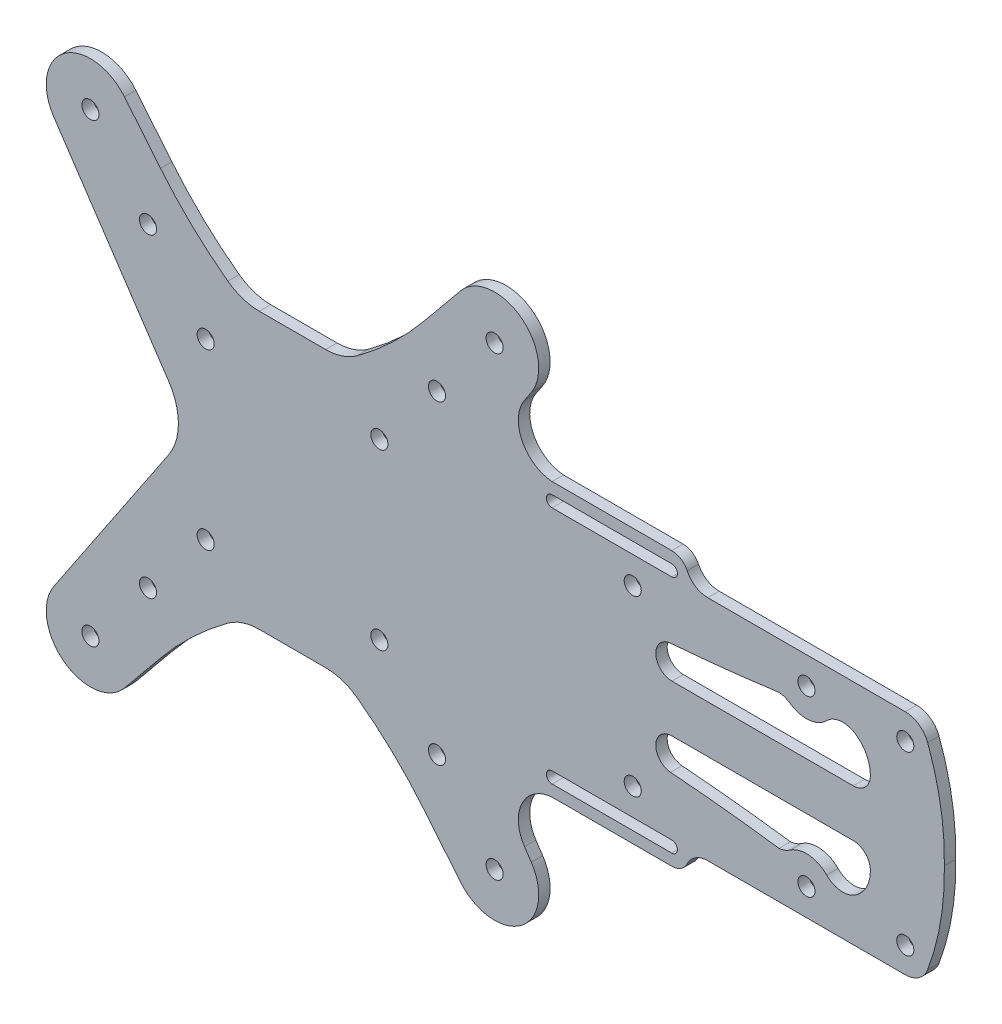
SolidWorks part; units mm, degrees
ref_plane "Alzado" through (0, 0, 0) normal (0, 0, 1) x (1, 0, 0)
ref_plane "Planta" through (0, 0, 0) normal (0, 1, 0) x (1, 0, 0)
ref_plane "Vista lateral" through (0, 0, 0) normal (1, 0, 0) x (0, 0, -1)
sketch "Croquis1" plane through (0, 0, 0) normal (0, 0, 1) x (1, 0, 0)
  line L0 (-41.9317, 35.7196) -> (-21.7292, 5.5661)
  line L1 (29.5025, -44.95) -> (23.1779, -37.2438)
  line L2 (-21.7292, -5.5661) -> (-41.9317, -35.7196)
  line L3 (0, -24.1955) -> (5.8264, -24.1955)
  line L4 (107.6126, 20) -> (72.9212, 20)
  line L5 (41.9317, -35.7196) -> (40.7426, -33.9448)
  line L6 (98.4739, 4.166) -> (66.6296, 4.166)
  line L7 (-29.5025, -44.95) -> (-23.1777, -37.2438)
  line L8 (40.7426, 33.9448) -> (41.9317, 35.7196)
  line L9 (45.5967, -24) -> (66.5967, -24)
  line L10 (29.5025, 44.95) -> (23.1777, 37.2438)
  line L11 (66.5967, -22) -> (45.5967, -22)
  line L12 (-23.1779, 37.2438) -> (-29.5025, 44.95)
  line L13 (0, 24.1955) -> (-5.8264, 24.1955)
  line L15 (66.5967, 24) -> (45.5967, 24)
  line L16 (-5.8264, -24.1955) -> (0, -24.1955)
  line L17 (45.5967, -20) -> (66.5967, -20)
  line L18 (5.8264, 24.1955) -> (0, 24.1955)
  line L19 (66.5967, 22) -> (45.5967, 22)
  line L21 (98.4739, -4.166) -> (66.6296, -4.166)
  line L22 (45.5967, 20) -> (66.5967, 20)
  line L23 (72.9212, -20) -> (107.6126, -20)
  circle A0 centre (59.75, -15.25) radius 1.5
  circle A1 centre (-15.25, -15.25) radius 1.5
  arc A2 (41.9317, 35.7196) -> (29.5025, 44.95) centre (35.4932, 40.0333) ccw
  arc A3 (5.8264, 24.1955) -> (11.353, 26.0087) centre (5.8264, 33.5248) ccw
  arc A4 (45.5967, -24) -> (40.7426, -33.9448) centre (46.0592, -30.3827) ccw
  circle A5 centre (35.4932, -40.0333) radius 1.5
  arc A6 (40.7426, 33.9448) -> (45.5967, 24) centre (46.0592, 30.3827) ccw
  arc A7 (-23.1779, 37.2438) -> (-11.353, 26.0087) centre (27.1524, 78.376) ccw
  arc A8 (98.9953, 12.1622) -> (93.8054, 11.7345) centre (96.6498, 8.922) ccw
  arc A9 (87.384, 11.1529) -> (93.8054, 11.7345) centre (90.25, 15.25) ccw
  circle A10 centre (107.6126, -15.5) radius 1.5
  arc A11 (101.4708, -7.03) -> (98.4739, -4.166) centre (98.4739, -7.166) ccw
  arc A12 (66.409, 9.8185) -> (66.6296, 4.166) centre (66.6296, 6.9965) ccw
  circle A13 centre (-35.4932, -40.0333) radius 1.5
  arc A14 (111.5451, 17.2675) -> (107.6126, 20) centre (107.6126, 15.804) ccw
  arc A15 (-21.7292, -5.5661) -> (-21.7292, 5.5661) centre (-30.037, 0) ccw
  arc A16 (93.8054, -11.7345) -> (98.9953, -12.1622) centre (96.6498, -8.922) ccw
  arc A17 (114.474, 0) -> (111.5451, 17.2675) centre (67.8434, 0.9728) ccw
  arc A18 (98.4739, 4.166) -> (101.4708, 7.03) centre (98.4739, 7.166) ccw
  arc A19 (98.9953, -12.1622) -> (101.4708, -7.03) centre (95.477, -7.302) ccw
  arc A20 (45.5967, -20) -> (45.5967, -22) centre (45.5967, -21) ccw
  circle A21 centre (15.25, 15.25) radius 1.5
  arc A22 (69.3072, 22.2857) -> (66.5967, 24) centre (66.5967, 21) ccw
  arc A23 (87.384, 11.1529) -> (85.4465, 11.8595) centre (85.0912, 7.8753) ccw
  arc A24 (85.4465, -11.8595) -> (66.409, -9.8185) centre (40.5006, -341.2912) ccw
  arc A25 (69.3072, 22.2857) -> (72.9212, 20) centre (72.9212, 24) ccw
  arc A26 (-11.353, -26.0087) -> (-23.1777, -37.2438) centre (27.1528, -78.3757) ccw
  arc A27 (111.5451, -17.2675) -> (114.474, 0) centre (67.8434, -0.9728) ccw
  circle A28 centre (59.75, 15.25) radius 1.5
  circle A29 centre (-25.3716, -27.6416) radius 1.5
  circle A30 centre (-25.3716, 27.6416) radius 1.5
  arc A31 (-29.5025, 44.95) -> (-41.9317, 35.7196) centre (-35.4932, 40.0333) ccw
  circle A32 centre (35.4932, 40.0333) radius 1.5
  arc A33 (-11.353, 26.0087) -> (-5.8264, 24.1955) centre (-5.8264, 33.5248) ccw
  circle A34 centre (107.6126, 15.5) radius 1.5
  circle A35 centre (-35.4932, 40.0333) radius 1.5
  arc A36 (66.5967, 20) -> (66.5967, 22) centre (66.5967, 21) ccw
  circle A37 centre (90.25, -15.25) radius 1.5
  arc A38 (-5.8264, -24.1955) -> (-11.353, -26.0087) centre (-5.8264, -33.5248) ccw
  arc A39 (72.9212, -20) -> (69.3072, -22.2857) centre (72.9212, -24) ccw
  arc A40 (66.5967, -24) -> (69.3072, -22.2857) centre (66.5967, -21) ccw
  arc A41 (29.5025, -44.95) -> (41.9317, -35.7196) centre (35.4932, -40.0333) ccw
  arc A42 (85.4465, -11.8595) -> (87.384, -11.1529) centre (85.0912, -7.8753) ccw
  arc A43 (66.6296, -4.166) -> (66.409, -9.8185) centre (66.6296, -6.9965) ccw
  arc A44 (93.8054, -11.7345) -> (87.384, -11.1529) centre (90.25, -15.25) ccw
  arc A45 (11.353, -26.0087) -> (5.8264, -24.1955) centre (5.8264, -33.5248) ccw
  arc A46 (66.409, 9.8185) -> (85.4465, 11.8595) centre (40.5006, 341.2912) ccw
  circle A47 centre (90.25, 15.25) radius 1.5
  circle A48 centre (-15.25, 15.25) radius 1.5
  arc A49 (23.1779, -37.2438) -> (11.353, -26.0087) centre (-27.1524, -78.376) ccw
  circle A51 centre (25.3716, -27.6416) radius 1.5
  arc A52 (-41.9317, -35.7196) -> (-29.5025, -44.95) centre (-35.4932, -40.0333) ccw
  circle A53 centre (15.25, -15.25) radius 1.5
  circle A54 centre (25.3716, 27.6416) radius 1.5
  arc A55 (11.353, 26.0087) -> (23.1777, 37.2438) centre (-27.1528, 78.3757) ccw
  arc A56 (101.4708, 7.03) -> (98.9953, 12.1622) centre (95.477, 7.302) ccw
  arc A57 (45.5967, 22) -> (45.5967, 20) centre (45.5967, 21) ccw
  arc A58 (107.6126, -20) -> (111.5451, -17.2675) centre (107.6126, -15.804) ccw
  arc A59 (66.5967, -22) -> (66.5967, -20) centre (66.5967, -21) ccw
  point P3 (0, 0)
  point P4 (0, 0)
  point P5 (0, 0)
  point P6 (0, 0)
  point P7 (0, 0)
  point P8 (0, 0)
  point P9 (0, 0)
  point P10 (0, 0)
  point P11 (0, 0)
  point P12 (0, 0)
  point P13 (0, 0)
  point P14 (0, 0)
  point P15 (0, 0)
  point P16 (0, 0)
  point P17 (0, 0)
  point P18 (0, 0)
  point P19 (0, 0)
  point P20 (0, 0)
  point P21 (0, 0)
  point P22 (0, 0)
  point P23 (0, 0)
  point P24 (0, 0)
  point P25 (0, 0)
  point P26 (0, 0)
  point P27 (0, 0)
  point P28 (0, 0)
  point P29 (0, 0)
  point P30 (0, 0)
  point P31 (0, 0)
  point P32 (0, 0)
  point P33 (0, 0)
  point P34 (0, 0)
  point P35 (0, 0)
  point P36 (0, 0)
  point P37 (0, 0)
  point P38 (0, 0)
  point P39 (0, 0)
  point P40 (0, 0)
  point P41 (0, 0)
  point P42 (0, 0)
  point P43 (0, 0)
  point P44 (0, 0)
  point P45 (0, 0)
  point P46 (0, 0)
  point P47 (0, 0)
  point P48 (0, 0)
  point P49 (0, 0)
  point P50 (0, 0)
  point P51 (0, 0)
  point P52 (0, 0)
  point P53 (0, 0)
  point P54 (0, 0)
  point P55 (0, 0)
  point P56 (0, 0)
  point P57 (0, 0)
  point P58 (0, 0)
  point P59 (0, 0)
  point P60 (0, 0)
  point P61 (0, 0)
  point P62 (0, 0)
  point P63 (0, 0)
  point P64 (0, 0)
  point P65 (0, 0)
  point P66 (0, 0)
  point P67 (0, 0)
  point P68 (0, 0)
  point P69 (0, 0)
  point P70 (0, 0)
  point P71 (0, 0)
  point P72 (0, 0)
  point P73 (0, 0)
  point P74 (0, 0)
  point P75 (0, 0)
  point P76 (0, 0)
  point P77 (0, 0)
  point P78 (0, 0)
  point P79 (0, 0)
  point P80 (0, 0)
  point P81 (0, 0)
  point P82 (0, 0)
  point P83 (0, 0)
  point P84 (0, 0)
  point P85 (0, 0)
  point P86 (0, 0)
  point P87 (0, 0)
  point P88 (0, 0)
  point P89 (0, 0)
  point P90 (0, 0)
  point P91 (0, 0)
  point P92 (0, 0)
  point P93 (0, 0)
  point P94 (0, 0)
  point P95 (0, 0)
  point P96 (0, 0)
  point P97 (0, 0)
  point P98 (0, 0)
  point P99 (0, 0)
  point P100 (0, 0)
  point P101 (0, 0)
  point P102 (0, 0)
  point P103 (0, 0)
  point P104 (0, 0)
  point P105 (0, 0)
  point P106 (0, 0)
  point P107 (0, 0)
  point P108 (0, 0)
  point P109 (0, 0)
  point P110 (0, 0)
  point P111 (0, 0)
  point P112 (0, 0)
  point P113 (0, 0)
  point P114 (0, 0)
  point P115 (0, 0)
  point P116 (0, 0)
  point P117 (0, 0)
  point P118 (0, 0)
  point P119 (0, 0)
  point P120 (0, 0)
  point P121 (0, 0)
  point P122 (0, 0)
  point P123 (0, 0)
  point P124 (0, 0)
  point P125 (0, 0)
  point P126 (0, 0)
  point P127 (0, 0)
  point P128 (0, 0)
  point P129 (0, 0)
  point P130 (0, 0)
  point P131 (0, 0)
  point P132 (0, 0)
  point P133 (0, 0)
  point P134 (0, 0)
  point P135 (0, 0)
  point P136 (0, 0)
  point P137 (0, 0)
  point P138 (0, 0)
  point P139 (0, 0)
  point P140 (0, 0)
  point P141 (0, 0)
  point P142 (0, 0)
  point P143 (0, 0)
  point P144 (0, 0)
  point P145 (0, 0)
  point P146 (0, 0)
  point P147 (0, 0)
  point P148 (0, 0)
  point P149 (0, 0)
  point P150 (0, 0)
  point P151 (0, 0)
  point P152 (0, 0)
  point P153 (0, 0)
  point P154 (0, 0)
  point P155 (0, 0)
  point P156 (0, 0)
  point P157 (0, 0)
  point P158 (0, 0)
  point P159 (0, 0)
  point P160 (0, 0)
  point P161 (0, 0)
  point P162 (0, 0)
  point P163 (0, 0)
  point P164 (0, 0)
  point P165 (0, 0)
  point P166 (0, 0)
  point P167 (0, 0)
  point P168 (0, 0)
  point P169 (0, 0)
  point P170 (0, 0)
  point P171 (0, 0)
  point P172 (0, 0)
  point P173 (0, 0)
  point P174 (0, 0)
  point P175 (0, 0)
  point P176 (0, 0)
  point P177 (0, 0)
  point P178 (0, 0)
  point P179 (0, 0)
  point P180 (0, 0)
  point P181 (0, 0)
  point P182 (0, 0)
  point P183 (0, 0)
  point P184 (0, 0)
  point P185 (0, 0)
  point P186 (0, 0)
  point P187 (0, 0)
  point P188 (0, 0)
  point P189 (0, 0)
  point P190 (0, 0)
  point P191 (0, 0)
  point P192 (0, 0)
  point P193 (0, 0)
  point P194 (0, 0)
  point P195 (0, 0)
  point P196 (0, 0)
  point P197 (0, 0)
  point P198 (0, 0)
  point P199 (0, 0)
  point P200 (0, 0)
  point P201 (0, 0)
  point P202 (0, 0)
  point P203 (0, 0)
  point P204 (0, 0)
  point P205 (0, 0)
  point P206 (0, 0)
  point P207 (0, 0)
  point P208 (0, 0)
  point P209 (0, 0)
  point P210 (0, 0)
  point P211 (0, 0)
  point P212 (0, 0)
  point P213 (0, 0)
  point P214 (0, 0)
  point P215 (0, 0)
  point P216 (0, 0)
  point P217 (0, 0)
  point P218 (0, 0)
  point P219 (0, 0)
  point P220 (0, 0)
  point P221 (0, 0)
  point P222 (0, 0)
  point P223 (0, 0)
  point P224 (0, 0)
  point P225 (0, 0)
  point P226 (0, 0)
  point P227 (0, 0)
  point P228 (0, 0)
  point P229 (0, 0)
  point P230 (0, 0)
  point P231 (0, 0)
  point P232 (0, 0)
  point P233 (0, 0)
  point P234 (0, 0)
  point P235 (0, 0)
  point P236 (0, 0)
  point P237 (0, 0)
  point P238 (0, 0)
  point P239 (0, 0)
  point P240 (0, 0)
  point P241 (0, 0)
  point P242 (0, 0)
  point P243 (0, 0)
  point P244 (0, 0)
  point P245 (0, 0)
  point P246 (0, 0)
  point P247 (0, 0)
  point P248 (0, 0)
  point P249 (0, 0)
  point P250 (0, 0)
  point P251 (0, 0)
  point P252 (0, 0)
  point P253 (0, 0)
  point P254 (0, 0)
  point P255 (0, 0)
  point P256 (0, 0)
  point P257 (0, 0)
  point P258 (0, 0)
  point P259 (0, 0)
  point P260 (0, 0)
  point P261 (0, 0)
  point P262 (0, 0)
  point P263 (0, 0)
  point P264 (0, 0)
  point P265 (0, 0)
  point P266 (0, 0)
  point P267 (0, 0)
  point P268 (0, 0)
  point P269 (0, 0)
  point P270 (0, 0)
  point P271 (0, 0)
  point P272 (0, 0)
  point P273 (0, 0)
  point P274 (0, 0)
  point P275 (0, 0)
  point P276 (0, 0)
  point P277 (0, 0)
  point P278 (0, 0)
  point P279 (0, 0)
  point P280 (0, 0)
  point P281 (0, 0)
  point P282 (0, 0)
  point P283 (0, 0)
  point P284 (0, 0)
  point P285 (0, 0)
  point P286 (0, 0)
  point P287 (0, 0)
  point P288 (0, 0)
  point P289 (0, 0)
  point P290 (0, 0)
  point P291 (0, 0)
  point P292 (0, 0)
  point P293 (0, 0)
  point P294 (0, 0)
  point P295 (0, 0)
  point P296 (0, 0)
  point P297 (0, 0)
  point P298 (0, 0)
  point P299 (0, 0)
  point P300 (0, 0)
  point P301 (0, 0)
  point P302 (0, 0)
  point P303 (0, 0)
  point P304 (0, 0)
  point P305 (0, 0)
  point P306 (0, 0)
  point P307 (0, 0)
  point P308 (0, 0)
  point P309 (0, 0)
  point P310 (0, 0)
  point P311 (0, 0)
  point P312 (0, 0)
  point P313 (0, 0)
  point P314 (0, 0)
  point P315 (0, 0)
  point P316 (0, 0)
  point P317 (0, 0)
  point P318 (0, 0)
  point P319 (0, 0)
  point P320 (0, 0)
  point P321 (0, 0)
  point P322 (0, 0)
  point P323 (0, 0)
  point P324 (0, 0)
  point P325 (0, 0)
  point P326 (0, 0)
  point P327 (0, 0)
  point P328 (0, 0)
  point P329 (0, 0)
  point P330 (0, 0)
  point P331 (0, 0)
  point P332 (0, 0)
  point P333 (0, 0)
  point P334 (0, 0)
  point P335 (0, 0)
  point P336 (0, 0)
  point P337 (0, 0)
  point P338 (0, 0)
  point P339 (0, 0)
  point P340 (0, 0)
  point P341 (0, 0)
  point P342 (0, 0)
  point P343 (0, 0)
  point P344 (0, 0)
  point P345 (0, 0)
  point P346 (0, 0)
  point P347 (0, 0)
  point P348 (0, 0)
  point P349 (0, 0)
  point P350 (0, 0)
  point P351 (0, 0)
  point P352 (0, 0)
  point P353 (0, 0)
  point P354 (0, 0)
  point P355 (0, 0)
  point P356 (0, 0)
  point P357 (0, 0)
  point P358 (0, 0)
  point P359 (0, 0)
  point P360 (0, 0)
  point P361 (0, 0)
  point P362 (0, 0)
  point P363 (0, 0)
  point P364 (0, 0)
  point P365 (0, 0)
  point P366 (0, 0)
  point P367 (0, 0)
  point P368 (0, 0)
  point P369 (0, 0)
  point P370 (0, 0)
  point P371 (0, 0)
  point P372 (0, 0)
  point P373 (0, 0)
  point P374 (0, 0)
  point P375 (0, 0)
  point P376 (0, 0)
  point P377 (0, 0)
  point P378 (0, 0)
  point P379 (0, 0)
  point P380 (0, 0)
  point P381 (0, 0)
  point P382 (0, 0)
  point P383 (0, 0)
  point P384 (0, 0)
  point P385 (0, 0)
  point P386 (0, 0)
  point P387 (0, 0)
  point P388 (0, 0)
  point P389 (0, 0)
  point P390 (0, 0)
  point P391 (0, 0)
  point P392 (0, 0)
  point P393 (0, 0)
  point P394 (0, 0)
  point P395 (0, 0)
  point P396 (0, 0)
  point P397 (0, 0)
  point P398 (0, 0)
  point P399 (0, 0)
  point P400 (0, 0)
  point P401 (0, 0)
  point P402 (0, 0)
  point P403 (0, 0)
  point P404 (0, 0)
  point P405 (0, 0)
  point P406 (0, 0)
  point P407 (0, 0)
  point P408 (0, 0)
  point P409 (0, 0)
  point P410 (0, 0)
  point P411 (0, 0)
  point P412 (0, 0)
  point P413 (0, 0)
  point P414 (0, 0)
  point P415 (0, 0)
  point P416 (0, 0)
  point P417 (0, 0)
  point P418 (0, 0)
  point P419 (0, 0)
  point P420 (0, 0)
  point P421 (0, 0)
  point P422 (0, 0)
  point P423 (0, 0)
  point P424 (0, 0)
  point P425 (0, 0)
  point P426 (0, 0)
  point P427 (0, 0)
  point P428 (0, 0)
  point P429 (0, 0)
  point P430 (0, 0)
  point P431 (0, 0)
  point P432 (0, 0)
  point P433 (0, 0)
  point P434 (0, 0)
  point P435 (0, 0)
  point P436 (0, 0)
  point P437 (0, 0)
  point P438 (0, 0)
  point P439 (0, 0)
  point P440 (0, 0)
  point P441 (0, 0)
  point P442 (0, 0)
  point P443 (0, 0)
  point P444 (0, 0)
  point P445 (0, 0)
  point P446 (0, 0)
  point P447 (0, 0)
  point P448 (0, 0)
  point P449 (0, 0)
  point P450 (0, 0)
  point P451 (0, 0)
  point P452 (0, 0)
  point P453 (0, 0)
  point P454 (0, 0)
  point P455 (0, 0)
  point P456 (0, 0)
  point P457 (0, 0)
  point P458 (0, 0)
  point P459 (0, 0)
  point P460 (0, 0)
  point P461 (0, 0)
  point P462 (0, 0)
  point P463 (0, 0)
  point P464 (0, 0)
  point P465 (0, 0)
  point P466 (0, 0)
  point P467 (0, 0)
  point P468 (0, 0)
  point P469 (0, 0)
  point P470 (0, 0)
  point P471 (0, 0)
  point P472 (0, 0)
  point P473 (0, 0)
  point P474 (0, 0)
  point P475 (0, 0)
  point P476 (0, 0)
  point P477 (0, 0)
  point P478 (0, 0)
  point P479 (0, 0)
  point P480 (0, 0)
  point P481 (0, 0)
  point P482 (0, 0)
  point P483 (0, 0)
  point P484 (0, 0)
  point P485 (0, 0)
  point P486 (0, 0)
  point P487 (0, 0)
  point P488 (0, 0)
  point P489 (0, 0)
  point P490 (0, 0)
  point P491 (0, 0)
  point P492 (0, 0)
  point P493 (0, 0)
  point P494 (0, 0)
  point P495 (0, 0)
  point P496 (0, 0)
  point P497 (0, 0)
  point P498 (0, 0)
  point P499 (0, 0)
  point P500 (0, 0)
  point P501 (0, 0)
  point P502 (0, 0)
  point P503 (0, 0)
  point P504 (0, 0)
  point P505 (0, 0)
  point P506 (0, 0)
  point P507 (0, 0)
  point P508 (0, 0)
  point P509 (0, 0)
  point P510 (0, 0)
  point P511 (0, 0)
  point P512 (0, 0)
  point P513 (0, 0)
  point P514 (0, 0)
  point P515 (0, 0)
  point P516 (0, 0)
  point P517 (0, 0)
  point P518 (0, 0)
  point P519 (0, 0)
  point P520 (0, 0)
  point P521 (0, 0)
  point P522 (0, 0)
  point P523 (0, 0)
  point P524 (0, 0)
  point P525 (0, 0)
  point P526 (0, 0)
  point P527 (0, 0)
  point P528 (0, 0)
  point P529 (0, 0)
  point P530 (0, 0)
  point P531 (0, 0)
  point P532 (0, 0)
  point P533 (0, 0)
  point P534 (0, 0)
  point P535 (0, 0)
  point P536 (0, 0)
  point P537 (0, 0)
  point P538 (0, 0)
  point P539 (0, 0)
  point P540 (0, 0)
  point P541 (0, 0)
  point P542 (0, 0)
  point P543 (0, 0)
  point P544 (0, 0)
  point P545 (0, 0)
  point P546 (0, 0)
  point P547 (0, 0)
  point P548 (0, 0)
  point P549 (0, 0)
  point P550 (0, 0)
  point P551 (0, 0)
  point P552 (0, 0)
  point P553 (0, 0)
  point P554 (0, 0)
  point P555 (0, 0)
  point P556 (0, 0)
  point P557 (0, 0)
  point P558 (0, 0)
  point P559 (0, 0)
  point P560 (0, 0)
  point P561 (0, 0)
  point P562 (0, 0)
  point P563 (0, 0)
  point P564 (0, 0)
  point P565 (0, 0)
  point P566 (0, 0)
  point P567 (0, 0)
  point P568 (0, 0)
  point P569 (0, 0)
  point P570 (0, 0)
  point P571 (0, 0)
  point P572 (0, 0)
  point P573 (0, 0)
  point P574 (0, 0)
  point P575 (0, 0)
  point P576 (0, 0)
  point P577 (0, 0)
  point P578 (0, 0)
  point P579 (0, 0)
  point P580 (0, 0)
  point P581 (0, 0)
  point P582 (0, 0)
  point P583 (0, 0)
  point P584 (0, 0)
  point P585 (0, 0)
  point P586 (0, 0)
  point P587 (0, 0)
  point P588 (0, 0)
  point P589 (0, 0)
  point P590 (0, 0)
  point P591 (0, 0)
  point P592 (0, 0)
  point P593 (0, 0)
  point P594 (0, 0)
  point P595 (0, 0)
  point P596 (0, 0)
  point P597 (0, 0)
  point P598 (0, 0)
  point P599 (0, 0)
  point P600 (0, 0)
  point P601 (0, 0)
  point P602 (0, 0)
  point P603 (0, 0)
  point P604 (0, 0)
  point P605 (0, 0)
  point P606 (0, 0)
  point P607 (0, 0)
  point P608 (0, 0)
  point P609 (0, 0)
  point P610 (0, 0)
  point P611 (0, 0)
  point P612 (0, 0)
  point P613 (0, 0)
  point P614 (0, 0)
  point P615 (0, 0)
  point P616 (0, 0)
  point P617 (0, 0)
  point P618 (0, 0)
  point P619 (0, 0)
  point P620 (0, 0)
  point P621 (0, 0)
  point P622 (0, 0)
  point P623 (0, 0)
  point P624 (0, 0)
  point P625 (0, 0)
  point P626 (0, 0)
  point P627 (0, 0)
  point P628 (0, 0)
  point P629 (0, 0)
  point P630 (0, 0)
  point P631 (0, 0)
  point P632 (0, 0)
  point P633 (0, 0)
  point P634 (0, 0)
  point P635 (0, 0)
  point P636 (0, 0)
  point P637 (0, 0)
  point P638 (0, 0)
  point P639 (0, 0)
  point P640 (0, 0)
  point P641 (0, 0)
  point P642 (0, 0)
  point P643 (0, 0)
  point P644 (0, 0)
  point P645 (0, 0)
  point P646 (0, 0)
  point P647 (0, 0)
  point P648 (0, 0)
  point P649 (0, 0)
  point P650 (0, 0)
  point P651 (0, 0)
  point P652 (0, 0)
  point P653 (0, 0)
  point P654 (0, 0)
  point P655 (0, 0)
  point P656 (0, 0)
  point P657 (0, 0)
  point P658 (0, 0)
  point P659 (0, 0)
  point P660 (0, 0)
  point P661 (0, 0)
  point P662 (0, 0)
  point P663 (0, 0)
  point P664 (0, 0)
  point P665 (0, 0)
  point P666 (0, 0)
  point P667 (0, 0)
  point P668 (0, 0)
  point P669 (0, 0)
  point P670 (0, 0)
  point P671 (0, 0)
  point P672 (0, 0)
  point P673 (0, 0)
  point P674 (0, 0)
  point P675 (0, 0)
  point P676 (0, 0)
  point P677 (0, 0)
  point P678 (0, 0)
  point P679 (0, 0)
  point P680 (0, 0)
  point P681 (0, 0)
  point P682 (0, 0)
  point P683 (0, 0)
  point P684 (0, 0)
  point P685 (0, 0)
  point P686 (0, 0)
  point P687 (0, 0)
  point P688 (0, 0)
  point P689 (0, 0)
  point P690 (0, 0)
  point P691 (0, 0)
  point P692 (0, 0)
  point P693 (0, 0)
  point P694 (0, 0)
  point P695 (0, 0)
  point P696 (0, 0)
  point P697 (0, 0)
  point P698 (0, 0)
  point P699 (0, 0)
  point P700 (0, 0)
  point P701 (0, 0)
  point P702 (0, 0)
  point P703 (0, 0)
  point P704 (0, 0)
  point P705 (0, 0)
  point P706 (0, 0)
  point P707 (0, 0)
  point P708 (0, 0)
  point P709 (0, 0)
  point P710 (0, 0)
  point P711 (0, 0)
  point P712 (0, 0)
  point P713 (0, 0)
  point P714 (0, 0)
  point P715 (0, 0)
  point P716 (0, 0)
  point P717 (0, 0)
  point P718 (0, 0)
  point P719 (0, 0)
  point P720 (0, 0)
  point P721 (0, 0)
  point P722 (0, 0)
  point P723 (0, 0)
  point P724 (0, 0)
  point P725 (0, 0)
  point P726 (0, 0)
  point P727 (0, 0)
  point P728 (0, 0)
  point P729 (0, 0)
  point P730 (0, 0)
  point P731 (0, 0)
  point P732 (0, 0)
  point P733 (0, 0)
  point P734 (0, 0)
  point P735 (0, 0)
  point P736 (0, 0)
  point P737 (0, 0)
  point P738 (0, 0)
  point P739 (0, 0)
  point P740 (0, 0)
  point P741 (0, 0)
  point P742 (0, 0)
  point P743 (0, 0)
  point P744 (0, 0)
  point P745 (0, 0)
  point P746 (0, 0)
  point P747 (0, 0)
  point P748 (0, 0)
  point P749 (0, 0)
  point P750 (0, 0)
  point P751 (0, 0)
  point P752 (0, 0)
  point P753 (0, 0)
  point P754 (0, 0)
  point P755 (0, 0)
  point P756 (0, 0)
  point P757 (0, 0)
  point P758 (0, 0)
  point P759 (0, 0)
  point P760 (0, 0)
  point P761 (0, 0)
  point P762 (0, 0)
  point P763 (0, 0)
  point P764 (0, 0)
  point P765 (0, 0)
  point P766 (0, 0)
  point P767 (0, 0)
  point P768 (0, 0)
  point P769 (0, 0)
  point P770 (0, 0)
  point P771 (0, 0)
  point P772 (0, 0)
  point P773 (0, 0)
  point P774 (0, 0)
  point P775 (0, 0)
  point P776 (0, 0)
  point P777 (0, 0)
  point P778 (0, 0)
  point P779 (0, 0)
  point P780 (0, 0)
  point P781 (0, 0)
  point P782 (0, 0)
  point P783 (0, 0)
  point P784 (0, 0)
  point P785 (0, 0)
  point P786 (0, 0)
  point P787 (0, 0)
  point P788 (0, 0)
  point P789 (0, 0)
  point P790 (0, 0)
  point P791 (0, 0)
  point P792 (0, 0)
  point P793 (0, 0)
  point P794 (0, 0)
  point P795 (0, 0)
  point P796 (0, 0)
  point P797 (0, 0)
  point P798 (0, 0)
  point P799 (0, 0)
  point P800 (0, 0)
  point P801 (0, 0)
  point P802 (0, 0)
  point P803 (0, 0)
  point P804 (0, 0)
  point P805 (0, 0)
  point P806 (0, 0)
  point P807 (0, 0)
  point P808 (0, 0)
  point P809 (0, 0)
  point P810 (0, 0)
  point P811 (0, 0)
  point P812 (0, 0)
  point P813 (0, 0)
  point P814 (0, 0)
  point P815 (0, 0)
  point P816 (0, 0)
  point P817 (0, 0)
  point P818 (0, 0)
  point P819 (0, 0)
  point P820 (0, 0)
  point P821 (0, 0)
  point P822 (0, 0)
  point P823 (0, 0)
  point P824 (0, 0)
  point P825 (0, 0)
  point P826 (0, 0)
  point P827 (0, 0)
  point P828 (0, 0)
  point P829 (0, 0)
  point P830 (0, 0)
  point P831 (0, 0)
  point P832 (0, 0)
  point P833 (0, 0)
  point P834 (0, 0)
  point P835 (0, 0)
  point P836 (0, 0)
  point P837 (0, 0)
  point P838 (0, 0)
  point P839 (0, 0)
  point P840 (0, 0)
  point P841 (0, 0)
  point P842 (0, 0)
  point P843 (0, 0)
  point P844 (0, 0)
  point P845 (0, 0)
  point P846 (0, 0)
  point P847 (0, 0)
  point P848 (0, 0)
  point P849 (0, 0)
  point P850 (0, 0)
  point P851 (0, 0)
  point P852 (0, 0)
  point P853 (0, 0)
  point P854 (0, 0)
  point P855 (0, 0)
  point P856 (0, 0)
  point P857 (0, 0)
  point P858 (0, 0)
  point P859 (0, 0)
  point P860 (0, 0)
  point P861 (0, 0)
  point P862 (0, 0)
  point P863 (0, 0)
  point P864 (0, 0)
  point P865 (0, 0)
  point P866 (0, 0)
  point P867 (0, 0)
  point P868 (0, 0)
  point P869 (0, 0)
  point P870 (0, 0)
  point P871 (0, 0)
  point P872 (0, 0)
  point P873 (0, 0)
  point P874 (0, 0)
  point P875 (0, 0)
  point P876 (0, 0)
  point P877 (0, 0)
  point P878 (0, 0)
  point P879 (0, 0)
  point P880 (0, 0)
  point P881 (0, 0)
  point P882 (0, 0)
  point P883 (0, 0)
  point P884 (0, 0)
  point P885 (0, 0)
  point P886 (0, 0)
  point P887 (0, 0)
  point P888 (0, 0)
  point P889 (0, 0)
  point P890 (0, 0)
  point P891 (0, 0)
  point P892 (0, 0)
  point P893 (0, 0)
  point P894 (0, 0)
  point P895 (0, 0)
  point P896 (0, 0)
  point P897 (0, 0)
  point P898 (0, 0)
  point P899 (0, 0)
  point P900 (0, 0)
  point P901 (0, 0)
  point P902 (0, 0)
  point P903 (0, 0)
  point P904 (0, 0)
  point P905 (0, 0)
  point P906 (0, 0)
  point P907 (0, 0)
  point P908 (0, 0)
  point P909 (0, 0)
  point P910 (0, 0)
  point P911 (0, 0)
  point P912 (0, 0)
  point P913 (0, 0)
  point P914 (0, 0)
  point P915 (0, 0)
  point P916 (0, 0)
  point P917 (0, 0)
  point P918 (0, 0)
  point P919 (0, 0)
  point P920 (0, 0)
  point P921 (0, 0)
  point P922 (0, 0)
  point P923 (0, 0)
  point P924 (0, 0)
  point P925 (0, 0)
  point P926 (0, 0)
  point P927 (0, 0)
  point P928 (0, 0)
  point P929 (0, 0)
  point P930 (0, 0)
  point P931 (0, 0)
  point P932 (0, 0)
  point P933 (0, 0)
  point P934 (0, 0)
  point P935 (0, 0)
  point P936 (0, 0)
  point P937 (0, 0)
  point P938 (0, 0)
  point P939 (0, 0)
  point P940 (0, 0)
  point P941 (0, 0)
  point P942 (0, 0)
  point P943 (0, 0)
  point P944 (0, 0)
  point P945 (0, 0)
  point P946 (0, 0)
  point P947 (0, 0)
  point P948 (0, 0)
  point P949 (0, 0)
  point P950 (0, 0)
  point P951 (0, 0)
  point P952 (0, 0)
  point P953 (0, 0)
  point P954 (0, 0)
  point P955 (0, 0)
  point P956 (0, 0)
  point P957 (0, 0)
  point P958 (0, 0)
  point P959 (0, 0)
  point P960 (0, 0)
  point P961 (0, 0)
  point P962 (0, 0)
  point P963 (0, 0)
  point P964 (0, 0)
  point P965 (0, 0)
  point P966 (0, 0)
  point P967 (0, 0)
  point P968 (0, 0)
  point P969 (0, 0)
  point P970 (0, 0)
  point P971 (0, 0)
  point P972 (0, 0)
  point P973 (0, 0)
  point P974 (0, 0)
  point P975 (0, 0)
  point P976 (0, 0)
  point P977 (0, 0)
  point P978 (0, 0)
  point P979 (0, 0)
  point P980 (0, 0)
  point P981 (0, 0)
  point P982 (0, 0)
  point P983 (0, 0)
  point P984 (0, 0)
  point P985 (0, 0)
  point P986 (0, 0)
  point P987 (0, 0)
  point P988 (0, 0)
  point P989 (0, 0)
  point P990 (0, 0)
  point P991 (0, 0)
  point P992 (0, 0)
  point P993 (0, 0)
  point P994 (0, 0)
  point P995 (0, 0)
  point P996 (0, 0)
  point P997 (0, 0)
  point P998 (0, 0)
  point P999 (0, 0)
  point P1000 (0, 0)
  point P1001 (0, 0)
  point P1002 (0, 0)
  point P1003 (0, 0)
  point P1004 (0, 0)
  point P1005 (0, 0)
  point P1006 (0, 0)
  point P1007 (0, 0)
  point P1008 (0, 0)
  point P1009 (0, 0)
  point P1010 (0, 0)
  point P1011 (0, 0)
  point P1012 (0, 0)
  point P1013 (0, 0)
  point P1014 (0, 0)
  point P1015 (0, 0)
  point P1016 (0, 0)
  point P1017 (0, 0)
  point P1018 (0, 0)
  point P1019 (0, 0)
  point P1020 (0, 0)
  point P1021 (0, 0)
  point P1022 (0, 0)
  point P1023 (0, 0)
  point P1024 (0, 0)
  point P1025 (0, 0)
  point P1026 (0, 0)
  point P1027 (0, 0)
  point P1028 (0, 0)
  point P1029 (0, 0)
  point P1030 (0, 0)
  point P1031 (0, 0)
  point P1032 (0, 0)
  point P1033 (0, 0)
  point P1034 (0, 0)
  point P1035 (0, 0)
  point P1036 (0, 0)
  point P1037 (0, 0)
  point P1038 (0, 0)
  point P1039 (0, 0)
  point P1040 (0, 0)
  point P1041 (0, 0)
  point P1042 (0, 0)
  point P1043 (0, 0)
  point P1044 (0, 0)
  point P1045 (0, 0)
  point P1046 (0, 0)
  point P1047 (0, 0)
  point P1048 (0, 0)
  point P1049 (0, 0)
  point P1050 (0, 0)
  point P1051 (0, 0)
  point P1052 (0, 0)
  point P1053 (0, 0)
  point P1054 (0, 0)
  point P1055 (0, 0)
  point P1056 (0, 0)
  point P1057 (0, 0)
  point P1058 (0, 0)
  point P1059 (0, 0)
  point P1060 (0, 0)
  point P1061 (0, 0)
  point P1062 (0, 0)
  point P1063 (0, 0)
  point P1064 (0, 0)
  point P1065 (0, 0)
  point P1066 (0, 0)
  point P1067 (0, 0)
  point P1068 (0, 0)
  point P1069 (0, 0)
  point P1070 (0, 0)
  point P1071 (0, 0)
  point P1072 (0, 0)
  point P1073 (0, 0)
  point P1074 (0, 0)
  point P1075 (0, 0)
  point P1076 (0, 0)
  point P1077 (0, 0)
  point P1078 (0, 0)
  point P1079 (0, 0)
  point P1080 (0, 0)
  point P1081 (0, 0)
  point P1082 (0, 0)
  point P1083 (0, 0)
  point P1084 (0, 0)
  point P1085 (0, 0)
  point P1086 (0, 0)
  point P1087 (0, 0)
  point P1088 (0, 0)
  point P1089 (0, 0)
  point P1090 (0, 0)
  point P1091 (0, 0)
  point P1092 (0, 0)
  point P1093 (0, 0)
  point P1094 (0, 0)
  point P1095 (0, 0)
  point P1096 (0, 0)
  point P1097 (0, 0)
  point P1098 (0, 0)
  point P1099 (0, 0)
  point P1100 (0, 0)
  point P1101 (0, 0)
  point P1102 (0, 0)
  point P1103 (0, 0)
  point P1104 (0, 0)
  point P1105 (0, 0)
  point P1106 (0, 0)
  point P1107 (0, 0)
  point P1108 (0, 0)
  point P1109 (0, 0)
  point P1110 (0, 0)
  point P1111 (0, 0)
  point P1112 (0, 0)
  point P1113 (0, 0)
  point P1114 (0, 0)
  point P1115 (0, 0)
  point P1116 (0, 0)
  point P1117 (0, 0)
  point P1118 (0, 0)
  point P1119 (0, 0)
  point P1120 (0, 0)
  point P1121 (0, 0)
  point P1122 (0, 0)
  point P1123 (0, 0)
  point P1124 (0, 0)
  point P1125 (0, 0)
  point P1126 (0, 0)
  point P1127 (0, 0)
  point P1128 (0, 0)
  point P1129 (0, 0)
  point P1130 (0, 0)
  point P1131 (0, 0)
  point P1132 (0, 0)
  point P1133 (0, 0)
  point P1134 (0, 0)
  point P1135 (0, 0)
  point P1136 (0, 0)
  point P1137 (0, 0)
  point P1138 (0, 0)
  point P1139 (0, 0)
  point P1140 (0, 0)
  point P1141 (0, 0)
  point P1142 (0, 0)
  point P1143 (0, 0)
  point P1144 (0, 0)
  point P1145 (0, 0)
  point P1146 (0, 0)
  point P1147 (0, 0)
  point P1148 (0, 0)
  point P1149 (0, 0)
  point P1150 (0, 0)
  point P1151 (0, 0)
  point P1152 (0, 0)
  point P1153 (0, 0)
  point P1154 (0, 0)
  point P1155 (0, 0)
  point P1156 (0, 0)
  point P1157 (0, 0)
  point P1158 (0, 0)
  point P1159 (0, 0)
  point P1160 (0, 0)
  point P1161 (0, 0)
  point P1162 (0, 0)
  point P1163 (0, 0)
  point P1164 (0, 0)
  point P1165 (0, 0)
  point P1166 (0, 0)
  point P1167 (0, 0)
  point P1168 (0, 0)
  point P1169 (0, 0)
  point P1170 (0, 0)
  point P1171 (0, 0)
  point P1172 (0, 0)
  point P1173 (0, 0)
  point P1174 (0, 0)
  point P1175 (0, 0)
  point P1176 (0, 0)
  point P1177 (0, 0)
  point P1178 (0, 0)
  point P1179 (0, 0)
  point P1180 (0, 0)
  point P1181 (0, 0)
  point P1182 (0, 0)
  point P1183 (0, 0)
  point P1184 (0, 0)
  point P1185 (0, 0)
  point P1186 (0, 0)
  point P1187 (0, 0)
  point P1188 (0, 0)
  point P1189 (0, 0)
  point P1190 (0, 0)
  point P1191 (0, 0)
  point P1192 (0, 0)
  point P1193 (0, 0)
  point P1194 (0, 0)
  point P1195 (0, 0)
  point P1196 (0, 0)
  point P1197 (0, 0)
  point P1198 (0, 0)
  point P1199 (0, 0)
  point P1200 (0, 0)
  point P1201 (0, 0)
  point P1202 (0, 0)
  point P1203 (0, 0)
  point P1204 (0, 0)
  point P1205 (0, 0)
  point P1206 (0, 0)
  point P1207 (0, 0)
  point P1208 (0, 0)
  point P1209 (0, 0)
  point P1210 (0, 0)
  point P1211 (0, 0)
  point P1212 (0, 0)
  point P1213 (0, 0)
  point P1214 (0, 0)
  point P1215 (0, 0)
  point P1216 (0, 0)
  point P1217 (0, 0)
  point P1218 (0, 0)
  point P1219 (0, 0)
  point P1220 (0, 0)
  point P1221 (0, 0)
  point P1222 (0, 0)
  point P1223 (0, 0)
  point P1224 (0, 0)
  point P1225 (0, 0)
  point P1226 (0, 0)
  point P1227 (0, 0)
  point P1228 (0, 0)
  point P1229 (0, 0)
  point P1230 (0, 0)
  point P1231 (0, 0)
  point P1232 (0, 0)
  point P1233 (0, 0)
  point P1234 (0, 0)
  point P1235 (0, 0)
  point P1236 (0, 0)
  point P1237 (0, 0)
  point P1238 (0, 0)
  point P1239 (0, 0)
  point P1240 (0, 0)
  point P1241 (0, 0)
  point P1242 (0, 0)
  point P1243 (0, 0)
  point P1244 (0, 0)
  point P1245 (0, 0)
  point P1246 (0, 0)
  point P1247 (0, 0)
  point P1248 (0, 0)
  point P1249 (0, 0)
  point P1250 (0, 0)
  point P1251 (0, 0)
  point P1252 (0, 0)
  point P1253 (0, 0)
  point P1254 (0, 0)
  point P1255 (0, 0)
  point P1256 (0, 0)
  point P1257 (0, 0)
  point P1258 (0, 0)
  point P1259 (0, 0)
  point P1260 (0, 0)
  point P1261 (0, 0)
  point P1262 (0, 0)
  point P1263 (0, 0)
  point P1264 (0, 0)
  point P1265 (0, 0)
  point P1266 (0, 0)
  point P1267 (0, 0)
  point P1268 (0, 0)
  point P1269 (0, 0)
  point P1270 (0, 0)
  point P1271 (0, 0)
  point P1272 (0, 0)
  point P1273 (0, 0)
  point P1274 (0, 0)
  point P1275 (0, 0)
  point P1276 (0, 0)
  point P1277 (0, 0)
  point P1278 (0, 0)
  point P1279 (0, 0)
  point P1280 (0, 0)
  point P1281 (0, 0)
  point P1282 (0, 0)
  point P1283 (0, 0)
  point P1284 (0, 0)
  point P1285 (0, 0)
  point P1286 (0, 0)
  point P1287 (0, 0)
  point P1288 (0, 0)
  point P1289 (0, 0)
  point P1290 (0, 0)
  point P1291 (0, 0)
  point P1292 (0, 0)
  point P1293 (0, 0)
  point P1294 (0, 0)
  point P1295 (0, 0)
  point P1296 (0, 0)
  point P1297 (0, 0)
  point P1298 (0, 0)
  point P1299 (0, 0)
  point P1300 (0, 0)
  point P1301 (0, 0)
  point P1302 (0, 0)
  point P1303 (0, 0)
  point P1304 (0, 0)
  point P1305 (0, 0)
  point P1306 (0, 0)
  point P1307 (0, 0)
  point P1308 (0, 0)
  point P1309 (0, 0)
  point P1310 (0, 0)
  point P1311 (0, 0)
  point P1312 (0, 0)
  point P1313 (0, 0)
  point P1314 (0, 0)
  point P1315 (0, 0)
  point P1316 (0, 0)
  point P1317 (0, 0)
  point P1318 (0, 0)
  point P1319 (0, 0)
  point P1320 (0, 0)
  point P1321 (0, 0)
  point P1322 (0, 0)
  point P1323 (0, 0)
  point P1324 (0, 0)
  point P1325 (0, 0)
  point P1326 (0, 0)
  point P1327 (0, 0)
  point P1328 (0, 0)
  point P1329 (0, 0)
  point P1330 (0, 0)
  point P1331 (0, 0)
  point P1332 (0, 0)
  point P1333 (0, 0)
  point P1334 (0, 0)
  point P1335 (0, 0)
  point P1336 (0, 0)
  point P1337 (0, 0)
  point P1338 (0, 0)
  point P1339 (0, 0)
  point P1340 (0, 0)
  point P1341 (0, 0)
  point P1342 (0, 0)
  point P1343 (0, 0)
  point P1344 (0, 0)
  point P1345 (0, 0)
  point P1346 (0, 0)
  point P1347 (0, 0)
  point P1348 (0, 0)
  point P1349 (0, 0)
  point P1350 (0, 0)
  point P1351 (0, 0)
  point P1352 (0, 0)
  point P1353 (0, 0)
  point P1354 (0, 0)
  point P1355 (0, 0)
  point P1356 (0, 0)
  point P1357 (0, 0)
  point P1358 (0, 0)
  point P1359 (0, 0)
  point P1360 (0, 0)
  point P1361 (0, 0)
  point P1362 (0, 0)
  point P1363 (0, 0)
  point P1364 (0, 0)
  point P1365 (0, 0)
  point P1366 (0, 0)
  point P1367 (0, 0)
  point P1368 (0, 0)
  point P1369 (0, 0)
  point P1370 (0, 0)
  point P1371 (0, 0)
  point P1372 (0, 0)
  point P1373 (0, 0)
  point P1374 (0, 0)
  point P1375 (0, 0)
  point P1376 (0, 0)
  point P1377 (0, 0)
  point P1378 (0, 0)
  point P1379 (0, 0)
  point P1380 (0, 0)
  point P1381 (0, 0)
  point P1382 (0, 0)
  point P1383 (0, 0)
  point P1384 (0, 0)
  point P1385 (0, 0)
  point P1386 (0, 0)
  point P1387 (0, 0)
  point P1388 (0, 0)
  point P1389 (0, 0)
  point P1390 (0, 0)
  point P1391 (0, 0)
  point P1392 (0, 0)
  point P1393 (0, 0)
  point P1394 (0, 0)
  point P1395 (0, 0)
  point P1396 (0, 0)
  point P1397 (0, 0)
  point P1398 (0, 0)
  point P1399 (0, 0)
  point P1400 (0, 0)
  point P1401 (0, 0)
  point P1402 (0, 0)
  point P1403 (0, 0)
  point P1404 (0, 0)
  point P1405 (0, 0)
  point P1406 (0, 0)
  point P1407 (0, 0)
  point P1408 (0, 0)
  point P1409 (0, 0)
  point P1410 (0, 0)
  point P1411 (0, 0)
  point P1412 (0, 0)
  point P1413 (0, 0)
  point P1414 (0, 0)
  point P1415 (0, 0)
  point P1416 (0, 0)
  point P1417 (0, 0)
  point P1418 (0, 0)
  point P1419 (0, 0)
  point P1420 (0, 0)
  point P1421 (0, 0)
  point P1422 (0, 0)
  point P1423 (0, 0)
  point P1424 (0, 0)
  point P1425 (0, 0)
  point P1426 (0, 0)
  point P1427 (0, 0)
  point P1428 (0, 0)
  point P1429 (0, 0)
  point P1430 (0, 0)
  point P1431 (0, 0)
  point P1432 (0, 0)
  point P1433 (0, 0)
  point P1434 (0, 0)
  point P1435 (0, 0)
  point P1436 (0, 0)
  point P1437 (0, 0)
  point P1438 (0, 0)
  point P1439 (0, 0)
  point P1440 (0, 0)
  point P1441 (0, 0)
  point P1442 (0, 0)
  point P1443 (0, 0)
  point P1444 (0, 0)
  point P1445 (0, 0)
  point P1446 (0, 0)
  point P1447 (0, 0)
  point P1448 (0, 0)
  point P1449 (0, 0)
  point P1450 (0, 0)
  point P1451 (0, 0)
  point P1452 (0, 0)
  point P1453 (0, 0)
  point P1454 (0, 0)
  point P1455 (0, 0)
  point P1456 (0, 0)
  point P1457 (0, 0)
  point P1458 (0, 0)
  point P1459 (0, 0)
  point P1460 (0, 0)
  point P1461 (0, 0)
  point P1462 (0, 0)
  point P1463 (0, 0)
  point P1464 (0, 0)
  point P1465 (0, 0)
  point P1466 (0, 0)
  point P1467 (0, 0)
  point P1468 (0, 0)
  point P1469 (0, 0)
  point P1470 (0, 0)
  point P1471 (0, 0)
  point P1472 (0, 0)
  point P1473 (0, 0)
  point P1474 (0, 0)
  point P1475 (0, 0)
  point P1476 (0, 0)
  point P1477 (0, 0)
  point P1478 (0, 0)
  point P1479 (0, 0)
  point P1480 (0, 0)
  point P1481 (0, 0)
  point P1482 (0, 0)
  point P1483 (0, 0)
  point P1484 (0, 0)
  point P1485 (0, 0)
  point P1486 (0, 0)
  point P1487 (0, 0)
  point P1488 (0, 0)
  point P1489 (0, 0)
  point P1490 (0, 0)
  point P1491 (0, 0)
  point P1492 (0, 0)
  point P1493 (0, 0)
  point P1494 (0, 0)
  point P1495 (0, 0)
  point P1496 (0, 0)
  point P1497 (0, 0)
  point P1498 (0, 0)
  point P1499 (0, 0)
  point P1500 (0, 0)
  point P1501 (0, 0)
  point P1502 (0, 0)
  point P1503 (0, 0)
  point P1504 (0, 0)
  point P1505 (0, 0)
  point P1506 (0, 0)
  point P1507 (0, 0)
  point P1508 (0, 0)
  point P1509 (0, 0)
  point P1510 (0, 0)
  point P1511 (0, 0)
  point P1512 (0, 0)
  point P1513 (0, 0)
  point P1514 (0, 0)
  point P1515 (0, 0)
  point P1516 (0, 0)
  point P1517 (0, 0)
  point P1518 (0, 0)
  point P1519 (0, 0)
  point P1520 (0, 0)
  point P1521 (0, 0)
  point P1522 (0, 0)
  point P1523 (0, 0)
  point P1524 (0, 0)
  point P1525 (0, 0)
  point P1526 (0, 0)
  point P1527 (0, 0)
  point P1528 (0, 0)
  point P1529 (0, 0)
  point P1530 (0, 0)
  point P1531 (0, 0)
  point P1532 (0, 0)
  point P1533 (0, 0)
  point P1534 (0, 0)
  point P1535 (0, 0)
  point P1536 (0, 0)
  point P1537 (0, 0)
  point P1538 (0, 0)
  point P1539 (0, 0)
  point P1540 (0, 0)
  point P1541 (0, 0)
  point P1542 (0, 0)
  point P1543 (0, 0)
  point P1544 (0, 0)
  point P1545 (0, 0)
  point P1546 (0, 0)
  point P1547 (0, 0)
  point P1548 (0, 0)
  point P1549 (0, 0)
  point P1550 (0, 0)
  point P1551 (0, 0)
  point P1552 (0, 0)
  point P1553 (0, 0)
  point P1554 (0, 0)
  point P1555 (0, 0)
  point P1556 (0, 0)
  point P1557 (0, 0)
  point P1558 (0, 0)
  point P1559 (0, 0)
  point P1560 (0, 0)
  point P1561 (0, 0)
  point P1562 (0, 0)
  point P1563 (0, 0)
  point P1564 (0, 0)
  point P1565 (0, 0)
  point P1566 (0, 0)
  point P1567 (0, 0)
  point P1568 (0, 0)
  point P1569 (0, 0)
  point P1570 (0, 0)
  point P1571 (0, 0)
  point P1572 (0, 0)
  point P1573 (0, 0)
  point P1574 (0, 0)
  point P1575 (0, 0)
  point P1576 (0, 0)
  point P1577 (0, 0)
  point P1578 (0, 0)
  point P1579 (0, 0)
  point P1580 (0, 0)
  point P1581 (0, 0)
  point P1582 (0, 0)
  point P1583 (0, 0)
  point P1584 (0, 0)
  point P1585 (0, 0)
  point P1586 (0, 0)
  point P1587 (0, 0)
  point P1588 (0, 0)
  point P1589 (0, 0)
  point P1590 (0, 0)
  point P1591 (0, 0)
  point P1592 (0, 0)
  point P1593 (0, 0)
  point P1594 (0, 0)
  point P1595 (0, 0)
  point P1596 (0, 0)
  point P1597 (0, 0)
  point P1598 (0, 0)
  point P1599 (0, 0)
  point P1600 (0, 0)
  point P1601 (0, 0)
  point P1602 (0, 0)
  point P1603 (0, 0)
  point P1604 (0, 0)
  point P1605 (0, 0)
  point P1606 (0, 0)
  point P1607 (0, 0)
  point P1608 (0, 0)
  point P1609 (0, 0)
  point P1610 (0, 0)
  point P1611 (0, 0)
  point P1612 (0, 0)
  point P1613 (0, 0)
  point P1614 (0, 0)
  point P1615 (0, 0)
  point P1616 (0, 0)
  point P1617 (0, 0)
  point P1618 (0, 0)
  point P1619 (0, 0)
  point P1620 (0, 0)
  point P1621 (0, 0)
  point P1622 (0, 0)
  point P1623 (0, 0)
  point P1624 (0, 0)
  point P1625 (0, 0)
  point P1626 (0, 0)
  point P1627 (0, 0)
  point P1628 (0, 0)
  point P1629 (0, 0)
  point P1630 (0, 0)
  point P1631 (0, 0)
  point P1632 (0, 0)
  point P1633 (0, 0)
  point P1634 (0, 0)
  point P1635 (0, 0)
  point P1636 (0, 0)
  point P1637 (0, 0)
  point P1638 (0, 0)
  point P1639 (0, 0)
  point P1640 (0, 0)
  point P1641 (0, 0)
  point P1642 (0, 0)
  point P1643 (0, 0)
  point P1644 (0, 0)
  point P1645 (0, 0)
  point P1646 (0, 0)
  point P1647 (0, 0)
  point P1648 (0, 0)
  point P1649 (0, 0)
  point P1650 (0, 0)
  point P1651 (0, 0)
  point P1652 (0, 0)
  point P1653 (0, 0)
  point P1654 (0, 0)
  point P1655 (0, 0)
  point P1656 (0, 0)
  point P1657 (0, 0)
  point P1658 (0, 0)
  point P1659 (0, 0)
  point P1660 (0, 0)
  point P1661 (0, 0)
  point P1662 (0, 0)
  point P1663 (0, 0)
  point P1664 (0, 0)
  point P1665 (0, 0)
  point P1666 (0, 0)
  point P1667 (0, 0)
  point P1668 (0, 0)
  point P1669 (0, 0)
  point P1670 (0, 0)
  point P1671 (0, 0)
  point P1672 (0, 0)
  point P1673 (0, 0)
  point P1674 (0, 0)
  point P1675 (0, 0)
  point P1676 (0, 0)
  point P1677 (0, 0)
  point P1678 (0, 0)
  point P1679 (0, 0)
  point P1680 (0, 0)
  point P1681 (0, 0)
  point P1682 (0, 0)
  point P1683 (0, 0)
  point P1684 (0, 0)
  point P1685 (0, 0)
  point P1686 (0, 0)
  point P1687 (0, 0)
  point P1688 (0, 0)
  point P1689 (0, 0)
  point P1690 (0, 0)
  point P1691 (0, 0)
  point P1692 (0, 0)
  point P1693 (0, 0)
  point P1694 (0, 0)
  point P1695 (0, 0)
  point P1696 (0, 0)
  point P1697 (0, 0)
  point P1698 (0, 0)
  point P1699 (0, 0)
  point P1700 (0, 0)
  point P1701 (0, 0)
  point P1702 (0, 0)
  point P1703 (0, 0)
  point P1704 (0, 0)
  point P1705 (0, 0)
  point P1706 (0, 0)
  point P1707 (0, 0)
  point P1708 (0, 0)
  point P1709 (0, 0)
  point P1710 (0, 0)
  point P1711 (0, 0)
  point P1712 (0, 0)
  point P1713 (0, 0)
  point P1714 (0, 0)
  point P1715 (0, 0)
  point P1716 (0, 0)
  point P1717 (0, 0)
  point P1718 (0, 0)
  point P1719 (0, 0)
  point P1720 (0, 0)
  point P1721 (0, 0)
  point P1722 (0, 0)
  point P1723 (0, 0)
  point P1724 (0, 0)
  point P1725 (0, 0)
  point P1726 (0, 0)
  point P1727 (0, 0)
  point P1728 (0, 0)
  point P1729 (0, 0)
  point P1730 (0, 0)
  point P1731 (0, 0)
  point P1732 (0, 0)
  point P1733 (0, 0)
  point P1734 (0, 0)
  point P1735 (0, 0)
  point P1736 (0, 0)
  point P1737 (0, 0)
  point P1738 (0, 0)
  point P1739 (0, 0)
  point P1740 (0, 0)
  point P1741 (0, 0)
  point P1742 (0, 0)
  point P1743 (0, 0)
  point P1744 (0, 0)
  point P1745 (0, 0)
  point P1746 (0, 0)
  point P1747 (0, 0)
  point P1748 (0, 0)
  point P1749 (0, 0)
  point P1750 (0, 0)
  point P1751 (0, 0)
  point P1752 (0, 0)
  point P1753 (0, 0)
  point P1754 (0, 0)
  point P1755 (0, 0)
  point P1756 (0, 0)
  point P1757 (0, 0)
  point P1758 (0, 0)
  point P1759 (0, 0)
  point P1760 (0, 0)
  point P1761 (0, 0)
  point P1762 (0, 0)
  point P1763 (0, 0)
  point P1764 (0, 0)
  point P1765 (0, 0)
  point P1766 (0, 0)
  point P1767 (0, 0)
  point P1768 (0, 0)
  point P1769 (0, 0)
  point P1770 (0, 0)
  point P1771 (0, 0)
  point P1772 (0, 0)
  point P1773 (0, 0)
  point P1774 (0, 0)
  point P1775 (0, 0)
  point P1776 (0, 0)
  point P1777 (0, 0)
  point P1778 (0, 0)
  point P1779 (0, 0)
  point P1780 (0, 0)
  point P1781 (0, 0)
  point P1782 (0, 0)
  point P1783 (0, 0)
  point P1784 (0, 0)
  point P1785 (0, 0)
  point P1786 (0, 0)
  point P1787 (0, 0)
  point P1788 (0, 0)
  point P1789 (0, 0)
  point P1790 (0, 0)
  point P1791 (0, 0)
  point P1792 (0, 0)
  point P1793 (0, 0)
  point P1794 (0, 0)
  point P1795 (0, 0)
  point P1796 (0, 0)
  point P1797 (0, 0)
  point P1798 (0, 0)
  point P1799 (0, 0)
  point P1800 (0, 0)
  point P1801 (0, 0)
  point P1802 (0, 0)
  point P1803 (0, 0)
  point P1804 (0, 0)
  point P1805 (0, 0)
  point P1806 (0, 0)
  point P1807 (0, 0)
  point P1808 (0, 0)
  point P1809 (0, 0)
  point P1810 (0, 0)
  point P1811 (0, 0)
  point P1812 (0, 0)
  point P1813 (0, 0)
  point P1814 (0, 0)
  point P1815 (0, 0)
  point P1816 (0, 0)
  point P1817 (0, 0)
  point P1818 (0, 0)
  point P1819 (0, 0)
  point P1820 (0, 0)
  point P1821 (0, 0)
  point P1822 (0, 0)
  point P1823 (0, 0)
  point P1824 (0, 0)
  point P1825 (0, 0)
  point P1826 (0, 0)
  point P1827 (0, 0)
  point P1828 (0, 0)
  point P1829 (0, 0)
  point P1830 (0, 0)
  point P1831 (0, 0)
  point P1832 (0, 0)
  point P1833 (0, 0)
  point P1834 (0, 0)
  point P1835 (0, 0)
  point P1836 (0, 0)
  point P1837 (0, 0)
  point P1838 (0, 0)
  point P1839 (0, 0)
  point P1840 (0, 0)
  point P1841 (0, 0)
  point P1842 (0, 0)
  point P1843 (0, 0)
  point P1844 (0, 0)
  point P1845 (0, 0)
  point P1846 (0, 0)
  point P1847 (0, 0)
  point P1848 (0, 0)
  point P1849 (0, 0)
  point P1850 (0, 0)
  point P1851 (0, 0)
  point P1852 (0, 0)
  point P1853 (0, 0)
  point P1854 (0, 0)
  point P1855 (0, 0)
  point P1856 (0, 0)
  point P1857 (0, 0)
  point P1858 (0, 0)
  point P1859 (0, 0)
  point P1860 (0, 0)
  point P1861 (0, 0)
  point P1862 (0, 0)
  point P1863 (0, 0)
  point P1864 (0, 0)
  point P1865 (0, 0)
  point P1866 (0, 0)
  point P1867 (0, 0)
  point P1868 (0, 0)
  point P1869 (0, 0)
  point P1870 (0, 0)
  point P1871 (0, 0)
  point P1872 (0, 0)
  point P1873 (0, 0)
  point P1874 (0, 0)
  point P1875 (0, 0)
  point P1876 (0, 0)
  point P1877 (0, 0)
  point P1878 (0, 0)
  point P1879 (0, 0)
  point P1880 (0, 0)
  point P1881 (0, 0)
  point P1882 (0, 0)
  point P1883 (0, 0)
  point P1884 (0, 0)
  point P1885 (0, 0)
  point P1886 (0, 0)
  point P1887 (0, 0)
  point P1888 (0, 0)
  point P1889 (0, 0)
  point P1890 (0, 0)
  point P1891 (0, 0)
  point P1892 (0, 0)
  point P1893 (0, 0)
  point P1894 (0, 0)
  point P1895 (0, 0)
  point P1896 (0, 0)
  point P1897 (0, 0)
  point P1898 (0, 0)
  point P1899 (0, 0)
  point P1900 (0, 0)
  point P1901 (0, 0)
  point P1902 (0, 0)
  point P1903 (0, 0)
  point P1904 (0, 0)
  point P1905 (0, 0)
  point P1906 (0, 0)
  point P1907 (0, 0)
  point P1908 (0, 0)
  point P1909 (0, 0)
  point P1910 (0, 0)
  point P1911 (0, 0)
  point P1912 (0, 0)
  point P1913 (0, 0)
  point P1914 (0, 0)
  point P1915 (0, 0)
  point P1916 (0, 0)
  point P1917 (0, 0)
  point P1918 (0, 0)
  point P1919 (0, 0)
  point P1920 (0, 0)
  point P1921 (0, 0)
  point P1922 (0, 0)
  point P1923 (0, 0)
  point P1924 (0, 0)
  point P1925 (0, 0)
  point P1926 (0, 0)
  point P1927 (0, 0)
  point P1928 (0, 0)
  point P1929 (0, 0)
  point P1930 (0, 0)
  point P1931 (0, 0)
  point P1932 (0, 0)
  point P1933 (0, 0)
  point P1934 (0, 0)
  point P1935 (0, 0)
  point P1936 (0, 0)
  point P1937 (0, 0)
  point P1938 (0, 0)
  point P1939 (0, 0)
  point P1940 (0, 0)
  point P1941 (0, 0)
  point P1942 (0, 0)
  point P1943 (0, 0)
  point P1944 (0, 0)
  point P1945 (0, 0)
  point P1946 (0, 0)
  point P1947 (0, 0)
  point P1948 (0, 0)
  point P1949 (0, 0)
  point P1950 (0, 0)
  point P1951 (0, 0)
  point P1952 (0, 0)
  point P1953 (0, 0)
  point P1954 (0, 0)
  point P1955 (0, 0)
  point P1956 (0, 0)
  point P1957 (0, 0)
  point P1958 (0, 0)
  point P1959 (0, 0)
  point P1960 (0, 0)
  point P1961 (0, 0)
  point P1962 (0, 0)
  point P1963 (0, 0)
  point P1964 (0, 0)
  point P1965 (0, 0)
  point P1966 (0, 0)
  point P1967 (0, 0)
  point P1968 (0, 0)
  point P1969 (0, 0)
  point P1970 (0, 0)
  point P1971 (0, 0)
  point P1972 (0, 0)
  point P1973 (0, 0)
  point P1974 (0, 0)
  point P1975 (0, 0)
  point P1976 (0, 0)
  point P1977 (0, 0)
  point P1978 (0, 0)
  point P1979 (0, 0)
  point P1980 (0, 0)
  point P1981 (0, 0)
  point P1982 (0, 0)
  point P1983 (0, 0)
  point P1984 (0, 0)
  point P1985 (0, 0)
  point P1986 (0, 0)
  point P1987 (0, 0)
  point P1988 (0, 0)
  point P1989 (0, 0)
  point P1990 (0, 0)
  point P1991 (0, 0)
  point P1992 (0, 0)
  point P1993 (0, 0)
  point P1994 (0, 0)
  point P1995 (0, 0)
  point P1996 (0, 0)
  point P1997 (0, 0)
  point P1998 (0, 0)
  point P1999 (0, 0)
  point P2000 (0, 0)
  point P2001 (0, 0)
  point P2002 (0, 0)
  point P2003 (0, 0)
  point P2004 (0, 0)
  point P2005 (0, 0)
  point P2006 (0, 0)
  point P2007 (0, 0)
  point P2008 (0, 0)
  point P2009 (0, 0)
  point P2010 (0, 0)
  point P2011 (0, 0)
  point P2012 (0, 0)
  point P2013 (0, 0)
  point P2014 (0, 0)
  point P2015 (0, 0)
  point P2016 (0, 0)
  point P2017 (0, 0)
  point P2018 (0, 0)
  point P2019 (0, 0)
  point P2020 (0, 0)
  point P2021 (0, 0)
  point P2022 (0, 0)
  point P2023 (0, 0)
  point P2024 (0, 0)
  point P2025 (0, 0)
  point P2026 (0, 0)
  point P2027 (0, 0)
  point P2028 (0, 0)
  point P2029 (0, 0)
  point P2030 (0, 0)
  point P2031 (0, 0)
  point P2032 (0, 0)
  point P2033 (0, 0)
  point P2034 (0, 0)
  point P2035 (0, 0)
  point P2036 (0, 0)
  point P2037 (0, 0)
  point P2038 (0, 0)
  point P2039 (0, 0)
  point P2040 (0, 0)
  point P2041 (0, 0)
  point P2042 (0, 0)
  point P2043 (0, 0)
  point P2044 (0, 0)
  point P2045 (0, 0)
  point P2046 (0, 0)
  point P2047 (0, 0)
  point P2048 (0, 0)
  point P2049 (0, 0)
  point P2050 (0, 0)
  point P2051 (0, 0)
  point P2052 (0, 0)
  point P2053 (0, 0)
  point P2054 (0, 0)
  point P2055 (0, 0)
  point P2056 (0, 0)
  point P2057 (0, 0)
  point P2058 (0, 0)
  point P2059 (0, 0)
  point P2060 (0, 0)
  point P2061 (0, 0)
  point P2062 (0, 0)
  point P2063 (0, 0)
  point P2064 (0, 0)
  point P2065 (0, 0)
  point P2066 (0, 0)
  point P2067 (0, 0)
  point P2068 (0, 0)
  point P2069 (0, 0)
  point P2070 (0, 0)
  point P2071 (0, 0)
  point P2072 (0, 0)
  point P2073 (0, 0)
  point P2074 (0, 0)
  point P2075 (0, 0)
  point P2076 (0, 0)
  point P2077 (0, 0)
  point P2078 (0, 0)
  point P2079 (0, 0)
  point P2080 (0, 0)
  point P2081 (0, 0)
  point P2082 (0, 0)
  point P2083 (0, 0)
  point P2084 (0, 0)
  point P2085 (0, 0)
  point P2086 (0, 0)
  point P2087 (0, 0)
  point P2088 (0, 0)
  point P2089 (0, 0)
  point P2090 (0, 0)
  point P2091 (0, 0)
  point P2092 (0, 0)
  point P2093 (0, 0)
  point P2094 (0, 0)
  point P2095 (0, 0)
  point P2096 (0, 0)
  point P2097 (0, 0)
  point P2098 (0, 0)
  point P2099 (0, 0)
  point P2100 (0, 0)
  point P2101 (0, 0)
  point P2102 (0, 0)
  point P2103 (0, 0)
  point P2104 (0, 0)
  point P2105 (0, 0)
  point P2106 (0, 0)
  point P2107 (0, 0)
  point P2108 (0, 0)
  point P2109 (0, 0)
  point P2110 (0, 0)
  point P2111 (0, 0)
  point P2112 (0, 0)
  point P2113 (0, 0)
  point P2114 (0, 0)
  point P2115 (0, 0)
  point P2116 (0, 0)
  point P2117 (0, 0)
  point P2118 (0, 0)
  point P2119 (0, 0)
  point P2120 (0, 0)
  point P2121 (0, 0)
  point P2122 (0, 0)
  point P2123 (0, 0)
  point P2124 (0, 0)
  point P2125 (0, 0)
  point P2126 (0, 0)
  point P2127 (0, 0)
  point P2128 (0, 0)
  point P2129 (0, 0)
  point P2130 (0, 0)
  point P2131 (0, 0)
  point P2132 (0, 0)
  point P2133 (0, 0)
  point P2134 (0, 0)
  point P2135 (0, 0)
  point P2136 (0, 0)
  point P2137 (0, 0)
  point P2138 (0, 0)
  point P2139 (0, 0)
  point P2140 (0, 0)
  point P2141 (0, 0)
  point P2142 (0, 0)
  point P2143 (0, 0)
  point P2144 (0, 0)
  point P2145 (0, 0)
  point P2146 (0, 0)
  point P2147 (0, 0)
  point P2148 (0, 0)
  point P2149 (0, 0)
  point P2150 (0, 0)
  point P2151 (0, 0)
  point P2152 (0, 0)
  point P2153 (0, 0)
  point P2154 (0, 0)
  point P2155 (0, 0)
  point P2156 (0, 0)
  point P2157 (0, 0)
  point P2158 (0, 0)
  point P2159 (0, 0)
  point P2160 (0, 0)
  point P2161 (0, 0)
  point P2162 (0, 0)
  point P2163 (0, 0)
  point P2164 (0, 0)
  point P2165 (0, 0)
  point P2166 (0, 0)
  point P2167 (0, 0)
  point P2168 (0, 0)
  point P2169 (0, 0)
  point P2170 (0, 0)
  point P2171 (0, 0)
  point P2172 (0, 0)
  point P2173 (0, 0)
  point P2174 (0, 0)
  point P2175 (0, 0)
  point P2176 (0, 0)
  point P2177 (0, 0)
  point P2178 (0, 0)
  point P2179 (0, 0)
  point P2180 (0, 0)
  point P2181 (0, 0)
  point P2182 (0, 0)
  point P2183 (0, 0)
  point P2184 (0, 0)
  point P2185 (0, 0)
  point P2186 (0, 0)
  point P2187 (0, 0)
  point P2188 (0, 0)
  point P2189 (0, 0)
  point P2190 (0, 0)
  point P2191 (0, 0)
  point P2192 (0, 0)
  point P2193 (0, 0)
  point P2194 (0, 0)
  point P2195 (0, 0)
  point P2196 (0, 0)
  point P2197 (0, 0)
  point P2198 (0, 0)
  point P2199 (0, 0)
  point P2200 (0, 0)
  point P2201 (0, 0)
  point P2202 (0, 0)
  point P2203 (0, 0)
  point P2204 (0, 0)
  point P2205 (0, 0)
  point P2206 (0, 0)
  point P2207 (0, 0)
  point P2208 (0, 0)
  point P2209 (0, 0)
  point P2210 (0, 0)
  point P2211 (0, 0)
  point P2212 (0, 0)
  point P2213 (0, 0)
  point P2214 (0, 0)
  point P2215 (0, 0)
  point P2216 (0, 0)
  point P2217 (0, 0)
  point P2218 (0, 0)
  point P2219 (0, 0)
  point P2220 (0, 0)
  point P2221 (0, 0)
  point P2222 (0, 0)
  point P2223 (0, 0)
  point P2224 (0, 0)
  point P2225 (0, 0)
  point P2226 (0, 0)
  point P2227 (0, 0)
  point P2228 (0, 0)
  point P2229 (0, 0)
  point P2230 (0, 0)
  point P2231 (0, 0)
  point P2232 (0, 0)
  point P2233 (0, 0)
  point P2234 (0, 0)
  point P2235 (0, 0)
  point P2236 (0, 0)
  point P2237 (0, 0)
  point P2238 (0, 0)
  point P2239 (0, 0)
  point P2240 (0, 0)
  point P2241 (0, 0)
  point P2242 (0, 0)
  point P2243 (0, 0)
  point P2244 (0, 0)
  point P2245 (0, 0)
  point P2246 (0, 0)
  point P2247 (0, 0)
  point P2248 (0, 0)
  point P2249 (0, 0)
  point P2250 (0, 0)
  point P2251 (0, 0)
  point P2252 (0, 0)
  point P2253 (0, 0)
  point P2254 (0, 0)
  point P2255 (0, 0)
  point P2256 (0, 0)
  point P2257 (0, 0)
  point P2258 (0, 0)
  point P2259 (0, 0)
  point P2260 (0, 0)
  point P2261 (0, 0)
  point P2262 (0, 0)
  point P2263 (0, 0)
  point P2264 (0, 0)
  point P2265 (0, 0)
  point P2266 (0, 0)
  point P2267 (0, 0)
  point P2268 (0, 0)
  point P2269 (0, 0)
  point P2270 (0, 0)
  point P2271 (0, 0)
  point P2272 (0, 0)
  point P2273 (0, 0)
  point P2274 (0, 0)
  point P2275 (0, 0)
  point P2276 (0, 0)
  point P2277 (0, 0)
  point P2278 (0, 0)
  point P2279 (0, 0)
  point P2280 (0, 0)
  point P2281 (0, 0)
  point P2282 (0, 0)
  point P2283 (0, 0)
  point P2284 (0, 0)
  point P2285 (0, 0)
  point P2286 (0, 0)
  point P2287 (0, 0)
  point P2288 (0, 0)
  point P2289 (0, 0)
  point P2290 (0, 0)
  point P2291 (0, 0)
  point P2292 (0, 0)
  point P2293 (0, 0)
  point P2294 (0, 0)
  point P2295 (0, 0)
  point P2296 (0, 0)
  point P2297 (0, 0)
  point P2298 (0, 0)
  point P2299 (0, 0)
  point P2300 (0, 0)
  point P2301 (0, 0)
  point P2302 (0, 0)
  point P2303 (0, 0)
  point P2304 (0, 0)
  point P2305 (0, 0)
  point P2306 (0, 0)
  point P2307 (0, 0)
  point P2308 (0, 0)
  point P2309 (0, 0)
  point P2310 (0, 0)
  point P2311 (0, 0)
  point P2312 (0, 0)
  point P2313 (0, 0)
  point P2314 (0, 0)
  point P2315 (0, 0)
  point P2316 (0, 0)
  point P2317 (0, 0)
  point P2318 (0, 0)
  point P2319 (0, 0)
  point P2320 (0, 0)
  point P2321 (0, 0)
  point P2322 (0, 0)
  point P2323 (0, 0)
  point P2324 (0, 0)
  point P2325 (0, 0)
  point P2326 (0, 0)
  point P2327 (0, 0)
  point P2328 (0, 0)
  point P2329 (0, 0)
  point P2330 (0, 0)
  point P2331 (0, 0)
  point P2332 (0, 0)
  point P2333 (0, 0)
  point P2334 (0, 0)
  point P2335 (0, 0)
  point P2336 (0, 0)
  point P2337 (0, 0)
  point P2338 (0, 0)
  point P2339 (0, 0)
  point P2340 (0, 0)
  point P2341 (0, 0)
  point P2342 (0, 0)
  point P2343 (0, 0)
  point P2344 (0, 0)
  point P2345 (0, 0)
  point P2346 (0, 0)
  point P2347 (0, 0)
  point P2348 (0, 0)
  point P2349 (0, 0)
  point P2350 (0, 0)
  point P2351 (0, 0)
  point P2352 (0, 0)
  point P2353 (0, 0)
  point P2354 (0, 0)
  point P2355 (0, 0)
  point P2356 (0, 0)
  point P2357 (0, 0)
  point P2358 (0, 0)
  point P2359 (0, 0)
  point P2360 (0, 0)
  point P2361 (0, 0)
  point P2362 (0, 0)
  point P2363 (0, 0)
  point P2364 (0, 0)
  point P2365 (0, 0)
  point P2366 (0, 0)
  point P2367 (0, 0)
  point P2368 (0, 0)
  point P2369 (0, 0)
  point P2370 (0, 0)
  point P2371 (0, 0)
  point P2372 (0, 0)
  point P2373 (0, 0)
  point P2374 (0, 0)
  point P2375 (0, 0)
  point P2376 (0, 0)
  point P2377 (0, 0)
  point P2378 (0, 0)
  point P2379 (0, 0)
  point P2380 (0, 0)
  point P2381 (0, 0)
  point P2382 (0, 0)
  point P2383 (0, 0)
  point P2384 (0, 0)
  point P2385 (0, 0)
  point P2386 (0, 0)
  point P2387 (0, 0)
  point P2388 (0, 0)
  point P2389 (0, 0)
  point P2390 (0, 0)
  point P2391 (0, 0)
  point P2392 (0, 0)
  point P2393 (0, 0)
  point P2394 (0, 0)
  point P2395 (0, 0)
  point P2396 (0, 0)
  point P2397 (0, 0)
  point P2398 (0, 0)
  point P2399 (0, 0)
  point P2400 (0, 0)
  point P2401 (0, 0)
  point P2402 (0, 0)
  point P2403 (0, 0)
  point P2404 (0, 0)
  point P2405 (0, 0)
  point P2406 (0, 0)
  point P2407 (0, 0)
  point P2408 (0, 0)
  point P2409 (0, 0)
  point P2410 (0, 0)
  point P2411 (0, 0)
  point P2412 (0, 0)
  point P2413 (0, 0)
  point P2414 (0, 0)
  point P2415 (0, 0)
  point P2416 (0, 0)
  point P2417 (0, 0)
  point P2418 (0, 0)
  point P2419 (0, 0)
  point P2420 (0, 0)
  point P2421 (0, 0)
  point P2422 (0, 0)
  point P2423 (0, 0)
  point P2424 (0, 0)
  point P2425 (0, 0)
  point P2426 (0, 0)
  point P2427 (0, 0)
  point P2428 (0, 0)
  point P2429 (0, 0)
  point P2430 (0, 0)
  point P2431 (0, 0)
  point P2432 (0, 0)
  point P2433 (0, 0)
  point P2434 (0, 0)
  point P2435 (0, 0)
  point P2436 (0, 0)
  point P2437 (0, 0)
  point P2438 (0, 0)
  point P2439 (0, 0)
  point P2440 (0, 0)
  point P2441 (0, 0)
  point P2442 (0, 0)
  point P2443 (0, 0)
  point P2444 (0, 0)
  point P2445 (0, 0)
  point P2446 (0, 0)
  point P2447 (0, 0)
  point P2448 (0, 0)
  point P2449 (0, 0)
  point P2450 (0, 0)
  point P2451 (0, 0)
  point P2452 (0, 0)
  point P2453 (0, 0)
  point P2454 (0, 0)
  point P2455 (0, 0)
  point P2456 (0, 0)
  point P2457 (0, 0)
  point P2458 (0, 0)
  point P2459 (0, 0)
  point P2460 (0, 0)
  point P2461 (0, 0)
  point P2462 (0, 0)
extrude "Saliente-Extruir1" add sketch "Croquis1" along normal blind 2
